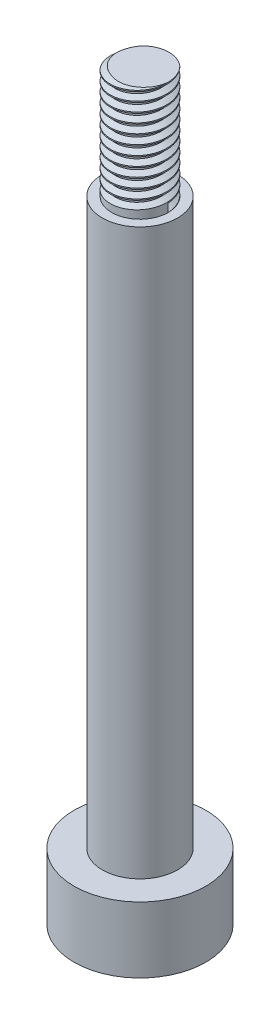
SolidWorks part; units mm, degrees
ref_plane "前视基准面" through (0, 0, 0) normal (0, 0, 1) x (1, 0, 0)
ref_plane "上视基准面" through (0, 0, 0) normal (0, 1, 0) x (1, 0, 0)
ref_plane "右视基准面" through (0, 0, 0) normal (1, 0, 0) x (0, 0, -1)
sketch "草图1" plane through (0, 0, 0) normal (0, 1, 0) x (1, 0, 0)
  circle A0 centre (0, 0) radius 3.5
  dimension "D1" = 7
extrude "凸台-拉伸1" add sketch "草图1" along normal blind 3.5
sketch "草图2" plane through (0, 3.5, 0) normal (0, 1, 0) x (1, 0, 0)
  circle A0 centre (0, 0) radius 2
  dimension "D1" = 4
extrude "凸台-拉伸2" add sketch "草图2" along normal blind 30
sketch "草图3" plane through (0, 33.5, 0) normal (0, 1, 0) x (1, 0, 0)
  circle A0 centre (0, 0) radius 1.5
  dimension "D1" = 3
extrude "凸台-拉伸3" add sketch "草图3" along normal blind 6
thread "螺纹线1" pitch 0.5 method cut profile "螺纹线轮廓1" start angle 0, offset 0, length 10, pitch 0.5, diameter 3
ref_plane "基准面1" through (1.5, 33.5, 0) normal (0, 0, 1) x (1, 0, 0)
sketch "螺纹线轮廓1" plane through (1.5, 33.5, 0) normal (0, 0, 1) x (1, 0, 0)
  line L0 (0, 0) -> (0, 0.5) construction
  line L11 (0, 0) -> (0, 0.4375)
  line L12 (0, 0.4375) -> (-0.2706, 0.2812)
  line L13 (-0.2706, 0.2812) -> (-0.2706, 0.1562)
  line L15 (-0.2706, 0.1562) -> (0, 0)
  line L17 (-0.2706, 0.2187) -> (0, 0.2187) construction
  point P2 (0, 0)
  dimension "Pitch" = 0.5
  dimension "Profile_Angle" = 60
  dimension "Profile_Land" = 0.125
  dimension "Profile_Height" = 0.2706
